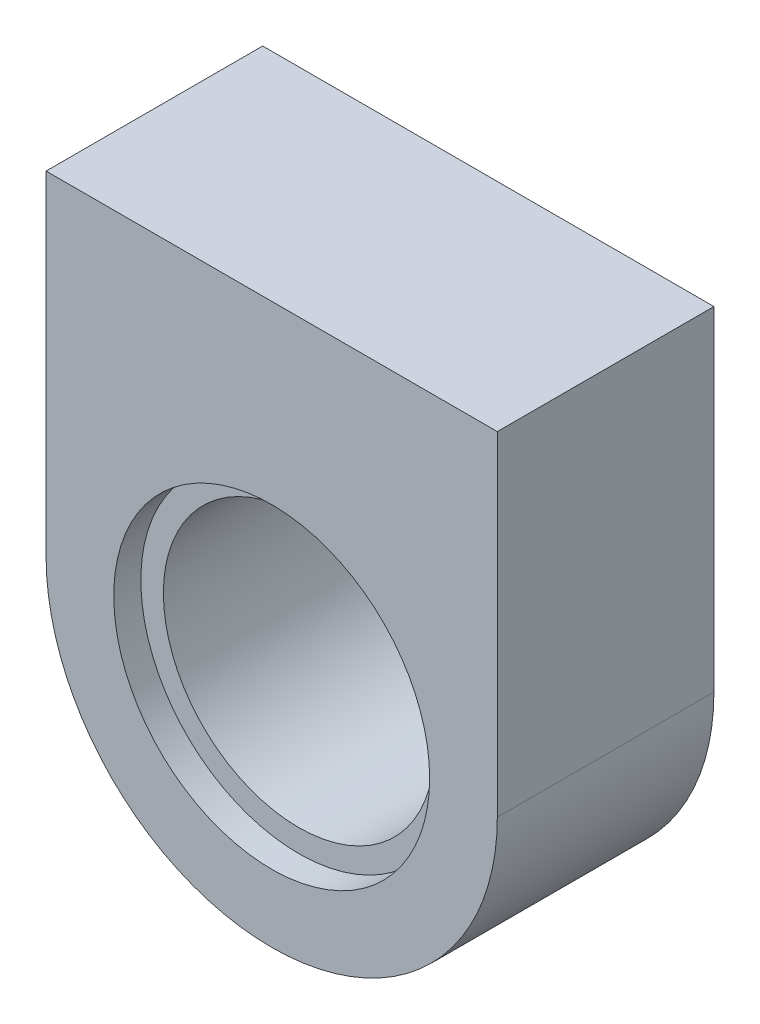
SolidWorks part; units mm, degrees
ref_plane "前视基准面" through (0, 0, 0) normal (0, 0, 1) x (1, 0, 0)
ref_plane "上视基准面" through (0, 0, 0) normal (0, 1, 0) x (1, 0, 0)
ref_plane "右视基准面" through (0, 0, 0) normal (1, 0, 0) x (0, 0, -1)
sketch "草图1" plane through (0, 0, 0) normal (0, 0, 1) x (1, 0, 0)
  line L1 (0, 0) -> (50, 0)
  line L2 (0, 0) -> (0, -62)
  line L3 (0, -62) -> (50, -62)
  line L4 (50, 0) -> (50, -62)
  dimension "D1" = 50
  dimension "D2" = 62
extrude "拉伸1" add sketch "草图1" along normal blind 24
fillet "圆角1" radius 25 2 edges at (0, -62, 12) (50, -62, 12)
sketch "草图2" plane through (0, 0, 0) normal (0, 0, -1) x (-1, 0, 0)
  circle A0 centre (-25, -37) radius 15
extrude "切除-拉伸1" cut sketch "草图2" against normal blind 30
sketch "草图3" plane through (0, 0, 24) normal (0, 0, 1) x (1, 0, 0)
  circle A0 centre (25, -37) radius 17.5
extrude "切除-拉伸2" cut sketch "草图3" against normal blind 3
